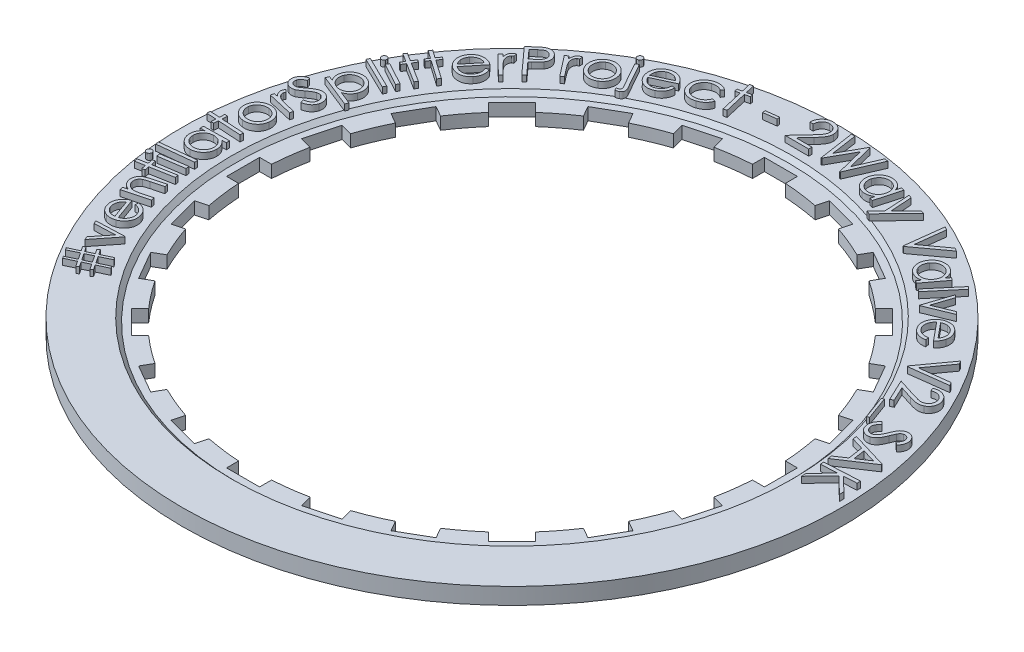
SolidWorks part; units mm, degrees
ref_plane "Ebene vorne" through (0, 0, 0) normal (0, 0, 1) x (1, 0, 0)
ref_plane "Ebene oben" through (0, 0, 0) normal (0, 1, 0) x (1, 0, 0)
ref_plane "Ebene rechts" through (0, 0, 0) normal (1, 0, 0) x (0, 0, -1)
sketch "Skizze1" plane through (0, 0, 0) normal (0, 1, 0) x (1, 0, 0)
  circle A0 centre (0, 0) radius 12.5
  circle A1 centre (0, 0) radius 16
  dimension "D1" = 25
  dimension "D2" = 32
extrude "Aufsatz-Linear austragen1" add sketch "Skizze1" along normal blind 0.8
sketch "Skizze2" plane through (0, 0.8, 0) normal (0, 1, 0) x (1, 0, 0)
  line L1 (-0.8014, 13.0557) -> (0.8014, 13.0557)
  line L2 (-0.8014, 13.0557) -> (-0.8014, 11.9443)
  line L3 (-0.8014, 11.9443) -> (0.8014, 11.9443)
  line L4 (0.8014, 13.0557) -> (0.8014, 11.9443)
  line L5 (-0.8014, 13.0557) -> (0.8014, 11.9443) construction
  line L6 (-0.8014, 11.9443) -> (0.8014, 13.0557) construction
  circle A0 centre (0, 0) radius 12.5 construction
  point P0 (0, 12.5)
extrude "Schnitt-Linear austragen1" cut sketch "Skizze2" against normal blind 0.8
pattern_circular "Kreismuster1" count 24 over 360 about axis through (0, 0.8, 0) along (0, 1, 0) of "Schnitt-Linear austragen1"
sketch "Skizze3" plane through (0, 0.8, 0) normal (0, 1, 0) x (1, 0, 0)
  circle A0 centre (0, 0) radius 13.6557
extrude "Schnitt-Linear austragen2" cut sketch "Skizze3" against normal blind 0.2
chamfer "Fase1" distance 0.25 angle 45 1 edges at (0, 0.6, 13.6557)
sketch "Skizze4" plane through (0, 0.8, 0) normal (0, 1, 0) x (1, 0, 0)
  circle A0 centre (0, 0) radius 14.0058 construction
  text T0 "#ventilatorSplitterProject - 2Way Valve V2_SAK" font "Century Gothic" height 1.7
extrude "Aufsatz-Linear austragen2" add sketch "Skizze4" along normal blind 0.3
